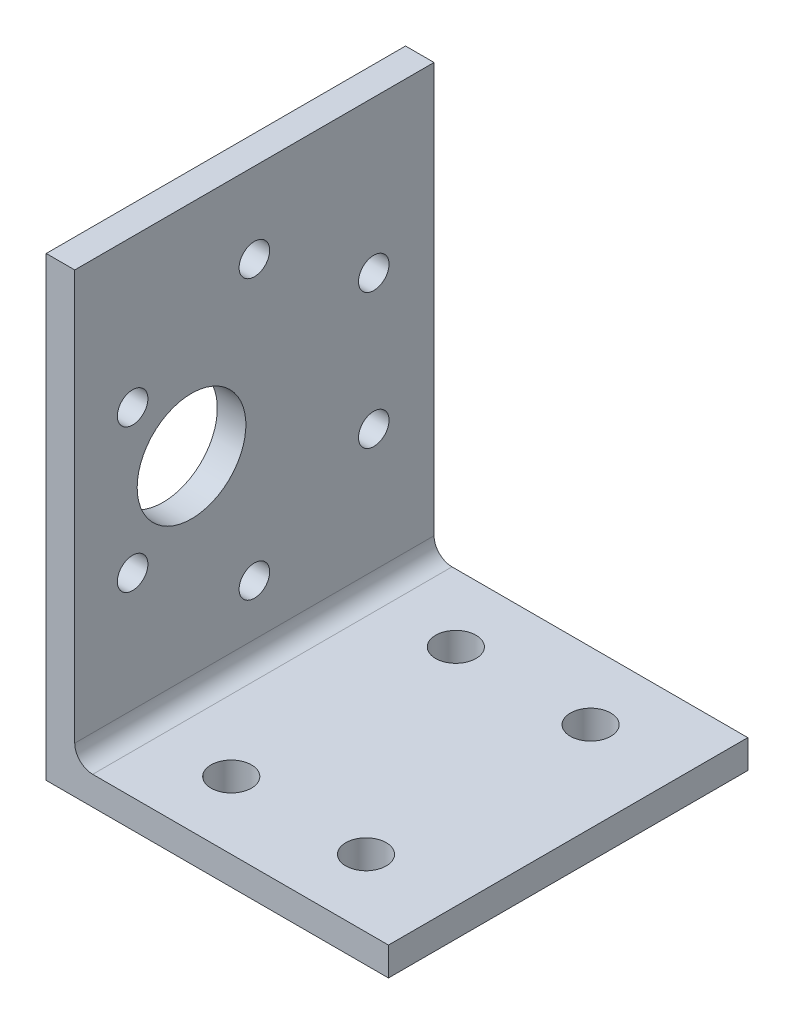
SolidWorks part; units mm, degrees
material "6061-T6 (SS)"
ref_plane "Front Plane" through (0, 0, 0) normal (0, 0, 1) x (1, 0, 0)
ref_plane "Top Plane" through (0, 0, 0) normal (0, 1, 0) x (1, 0, 0)
ref_plane "Right Plane" through (0, 0, 0) normal (1, 0, 0) x (0, 0, -1)
sketch "Sketch1" plane through (0, 0, 0) normal (0, 0, 1) x (1, 0, 0)
  line L0 (0, 0) -> (0, 50.8)
  line L1 (0, 50.8) -> (3.175, 50.8)
  line L2 (3.175, 50.8) -> (3.175, 3.175)
  line L3 (3.175, 3.175) -> (38.1, 3.175)
  line L4 (38.1, 3.175) -> (38.1, 0)
  line L5 (38.1, 0) -> (0, 0)
  dimension "D1" = 3.175
  dimension "D2" = 3.175
  dimension "D3" = 38.1
  dimension "D4" = 50.8
extrude "Boss-Extrude1" add sketch "Sketch1" along normal mid plane 40
fillet "Fillet1" radius 2 1 edges at (3.175, 3.175, 0)
sketch "Sketch10" plane through (0, 0, 0) normal (-1, 0, 0) x (0, 0, 1)
  line L0 (20, 0) -> (-20, 0) construction
  circle A0 centre (0.2647, 26.35) radius 15.5
  point P0 (0, 41.8477)
  point P2 (13.5538, 34.3281)
  point P4 (-13.2891, 18.8304)
  point P6 (0, 10.8523)
  point P17 (-13.2891, 33.8696)
  point P19 (13.5538, 18.3719)
  dimension "D1" = 31
  dimension "D2" = 60
  dimension "D3" = 60
  dimension "D4" = 26.35
hole_wizard "M3 Clearance Hole1" positions "Sketch10" profile "Sketch3" hole size "M3" standard "ANSI Metric" end condition through all
sketch "Sketch3" plane through (0, 41.8477, 0) normal (0, 1, 0) x (0, 0, 1)
  line L0 (0, 0) -> (0, 38.1)
  line L1 (0, 38.1) -> (1.7, 38.1)
  line L2 (1.7, 38.1) -> (1.7, 0)
  line L5 (1.7, 0) -> (0, 0)
  line L11 (0, -6.35) -> (0, 107.95) construction
  dimension "Thru Hole Dia." = 3.4
  dimension "Thru Hole Depth" = 38.1
sketch "Sketch6" plane through (0, 0, 0) normal (-1, 0, 0) x (0, 0, 1)
  line L0 (20, 0) -> (-20, 0) construction
  circle A0 centre (7, 26.35) radius 6.05
  circle A3 centre (0, 41.8477) radius 1.7 construction
  point P2 (4.8959, 25.4)
  dimension "D2" = 12.1
  dimension "D1" = 26.35
  dimension "D3" = 7
extrude "Cut-Extrude1" cut sketch "Sketch6" against normal through all
hole_wizard "M4 Clearance Hole1" positions "Sketch14" profile "Sketch12" hole size "M4" standard "ANSI Metric" end condition through all
sketch "Sketch14" plane through (0, 3.175, 0) normal (0, 1, 0) x (1, 0, 0)
  line L0 (38.1, 20) -> (5.175, 20) construction
  line L1 (38.1, -20) -> (38.1, 20) construction
  point P0 (13.1, -12.5)
  point P2 (28.1, -12.5)
  point P4 (28.1, 12.5)
  point P6 (13.1, 12.5)
  dimension "D1" = 15
  dimension "D2" = 25
  dimension "D3" = 7.5
  dimension "D4" = 10
sketch "Sketch12" plane through (13.1, 3.175, 12.5) normal (1, 0, 0) x (0, 0, 1)
  line L0 (0, 0) -> (0, 3.175)
  line L1 (0, 3.175) -> (2.25, 3.175)
  line L2 (2.25, 3.175) -> (2.25, 0)
  line L5 (2.25, 0) -> (0, 0)
  line L11 (0, -6.35) -> (0, 107.95) construction
  dimension "Thru Hole Dia." = 4.5
  dimension "Thru Hole Depth" = 3.175
